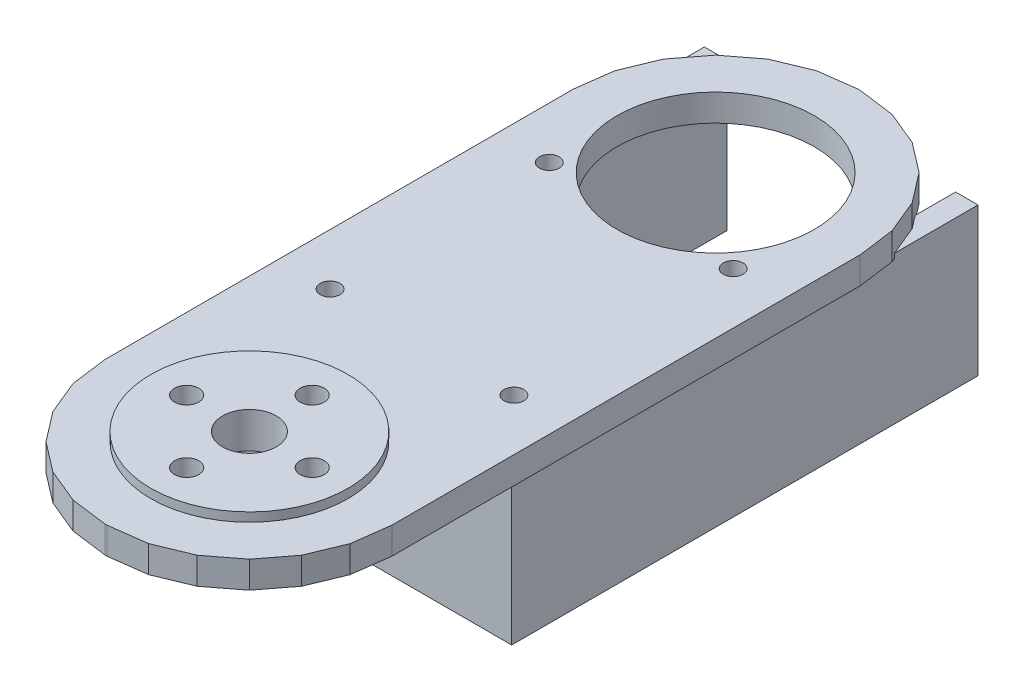
SolidWorks part; units mm, degrees
ref_plane "Front Plane" through (0, 0, 0) normal (0, 0, 1) x (1, 0, 0)
ref_plane "Top Plane" through (0, 0, 0) normal (0, 1, 0) x (1, 0, 0)
ref_plane "Right Plane" through (0, 0, 0) normal (1, 0, 0) x (0, 0, -1)
ref_plane "PY_m1_100" through (0, -1.1, 0) normal (0, 1, 0) x (1, 0, 0)
sketch "S_cyl1" plane through (0, -1.1, 0) normal (0, 1, 0) x (1, 0, 0)
  circle A0 centre (0, 0) radius 11
  dimension "D1_S_cyl1" = 22
extrude "Boss_1" add sketch "S_cyl1" along normal blind 1.1
ref_plane "PY_m4_000" through (0, -4, 0) normal (0, 1, 0) x (1, 0, 0)
sketch "S_prism2" plane through (0, -4, 0) normal (0, 1, 0) x (1, 0, 0)
  line L0 (-16, -0.1) -> (-15.458, -4.215)
  line L1 (-15.458, -4.215) -> (-13.87, -8.05)
  line L2 (-13.87, -8.05) -> (-11.343, -11.343)
  line L3 (-11.343, -11.343) -> (-8.05, -13.87)
  line L4 (-8.05, -13.87) -> (-4.215, -15.458)
  line L5 (-4.215, -15.458) -> (-0.1, -16)
  line L6 (-0.1, -16) -> (0.1, -16)
  line L7 (0.1, -16) -> (4.215, -15.458)
  line L8 (4.215, -15.458) -> (8.05, -13.87)
  line L9 (8.05, -13.87) -> (11.343, -11.343)
  line L10 (11.343, -11.343) -> (13.87, -8.05)
  line L11 (13.87, -8.05) -> (15.458, -4.215)
  line L12 (15.458, -4.215) -> (16, -0.1)
  line L13 (16, -0.1) -> (16, 52.1)
  line L14 (16, 52.1) -> (15.458, 56.215)
  line L15 (15.458, 56.215) -> (13.87, 60.05)
  line L16 (13.87, 60.05) -> (11.343, 63.343)
  line L17 (11.343, 63.343) -> (8.05, 65.87)
  line L18 (8.05, 65.87) -> (4.215, 67.458)
  line L19 (4.215, 67.458) -> (0.1, 68)
  line L20 (0.1, 68) -> (-0.1, 68)
  line L21 (-0.1, 68) -> (-4.215, 67.458)
  line L22 (-4.215, 67.458) -> (-8.05, 65.87)
  line L23 (-8.05, 65.87) -> (-11.343, 63.343)
  line L24 (-11.343, 63.343) -> (-13.87, 60.05)
  line L25 (-13.87, 60.05) -> (-15.458, 56.215)
  line L26 (-15.458, 56.215) -> (-16, 52.1)
  line L27 (-16, 52.1) -> (-16, -0.1)
  dimension "P1" = 16
  dimension "P2" = 0.1
  dimension "P3" = 15.458
  dimension "P4" = 4.215
  dimension "P5" = 13.87
  dimension "P6" = 8.05
  dimension "P7" = 11.343
  dimension "P8" = 11.343
  dimension "P9" = 8.05
  dimension "P10" = 13.87
  dimension "P11" = 4.215
  dimension "P12" = 15.458
  dimension "P13" = 0.1
  dimension "P14" = 16
  dimension "P15" = 0.1
  dimension "P16" = 16
  dimension "P17" = 4.215
  dimension "P18" = 15.458
  dimension "P19" = 8.05
  dimension "P20" = 13.87
  dimension "P21" = 11.343
  dimension "P22" = 11.343
  dimension "P23" = 13.87
  dimension "P24" = 8.05
  dimension "P25" = 15.458
  dimension "P26" = 4.215
  dimension "P27" = 16
  dimension "P28" = 0.1
  dimension "P29" = 16
  dimension "P30" = 52.1
  dimension "P31" = 15.458
  dimension "P32" = 56.215
  dimension "P33" = 13.87
  dimension "P34" = 60.05
  dimension "P35" = 11.343
  dimension "P36" = 63.343
  dimension "P37" = 8.05
  dimension "P38" = 65.87
  dimension "P39" = 4.215
  dimension "P40" = 67.458
  dimension "P41" = 0.1
  dimension "P42" = 68
  dimension "P43" = 0.1
  dimension "P44" = 68
  dimension "P45" = 4.215
  dimension "P46" = 67.458
  dimension "P47" = 8.05
  dimension "P48" = 65.87
  dimension "P49" = 11.343
  dimension "P50" = 63.343
  dimension "P51" = 13.87
  dimension "P52" = 60.05
  dimension "P53" = 15.458
  dimension "P54" = 56.215
  dimension "P55" = 16
  dimension "P56" = 52.1
extrude "Boss_2" add sketch "S_prism2" along normal blind 3
ref_plane "PZ_m66_000" through (0, 0, -66) normal (0, 0, 1) x (1, 0, 0)
sketch "S_box3" plane through (0, 0, -66) normal (0, 0, 1) x (1, 0, 0)
  line L0 (12.76, -20) -> (15.26, -20)
  line L1 (15.26, -20) -> (15.26, -3.5)
  line L2 (15.26, -3.5) -> (12.76, -3.5)
  line L3 (12.76, -3.5) -> (12.76, -20)
  dimension "P1" = 12.76
  dimension "P2" = 20
  dimension "P3" = 15.26
  dimension "P4" = 20
  dimension "P5" = 15.26
  dimension "P6" = 3.5
  dimension "P7" = 12.76
  dimension "P8" = 3.5
extrude "Boss_3" add sketch "S_box3" along normal blind 52.01
sketch "S_box4" plane through (0, 0, -66) normal (0, 0, 1) x (1, 0, 0)
  line L0 (-15.26, -20) -> (-12.76, -20)
  line L1 (-12.76, -20) -> (-12.76, -3.5)
  line L2 (-12.76, -3.5) -> (-15.26, -3.5)
  line L3 (-15.26, -3.5) -> (-15.26, -20)
  dimension "P1" = 15.26
  dimension "P2" = 20
  dimension "P3" = 12.76
  dimension "P4" = 20
  dimension "P5" = 12.76
  dimension "P6" = 3.5
  dimension "P7" = 15.26
  dimension "P8" = 3.5
extrude "Boss_4" add sketch "S_box4" along normal blind 52.01
ref_plane "PZ_m16_490" through (0, 0, -16.49) normal (0, 0, 1) x (1, 0, 0)
sketch "S_box5" plane through (0, 0, -16.49) normal (0, 0, 1) x (1, 0, 0)
  line L0 (-15.26, -20) -> (15.26, -20)
  line L1 (15.26, -20) -> (15.26, -3.5)
  line L2 (15.26, -3.5) -> (-15.26, -3.5)
  line L3 (-15.26, -3.5) -> (-15.26, -20)
  dimension "P1" = 15.26
  dimension "P2" = 20
  dimension "P3" = 15.26
  dimension "P4" = 20
  dimension "P5" = 15.26
  dimension "P6" = 3.5
  dimension "P7" = 15.26
  dimension "P8" = 3.5
extrude "Boss_5" add sketch "S_box5" along normal blind 2.5
ref_plane "PY_m4_100" through (0, -4.1, 0) normal (0, 1, 0) x (1, 0, 0)
sketch "S_hole6" plane through (0, -4.1, 0) normal (0, 1, 0) x (1, 0, 0)
  circle A0 centre (0, 0) radius 3
  dimension "D1_S_hole6" = 6
extrude "Hole_6" cut sketch "S_hole6" along normal blind 4.2
sketch "S_hole7" plane through (0, -4.1, 0) normal (0, 1, 0) x (1, 0, 0)
  circle A0 centre (7, 0) radius 1.35
  dimension "D1_S_hole7" = 2.7
  dimension "P2" = 7
extrude "Hole_7" cut sketch "S_hole7" along normal blind 4.2
sketch "S_hole8" plane through (0, -4.1, 0) normal (0, 1, 0) x (1, 0, 0)
  circle A0 centre (0, -7) radius 1.35
  dimension "D1_S_hole8" = 2.7
  dimension "P2" = 7
extrude "Hole_8" cut sketch "S_hole8" along normal blind 4.2
sketch "S_hole9" plane through (0, -4.1, 0) normal (0, 1, 0) x (1, 0, 0)
  circle A0 centre (-7, 0) radius 1.35
  dimension "D1_S_hole9" = 2.7
  dimension "P2" = 7
extrude "Hole_9" cut sketch "S_hole9" along normal blind 4.2
sketch "S_hole10" plane through (0, -4.1, 0) normal (0, 1, 0) x (1, 0, 0)
  circle A0 centre (0, 7) radius 1.35
  dimension "D1_S_hole10" = 2.7
  dimension "P2" = 7
extrude "Hole_10" cut sketch "S_hole10" along normal blind 4.2
sketch "S_hole11" plane through (0, -4.1, 0) normal (0, 1, 0) x (1, 0, 0)
  circle A0 centre (0, 52) radius 11
  dimension "D1_S_hole11" = 22
  dimension "P2" = 52
extrude "Hole_11" cut sketch "S_hole11" along normal blind 3.2
sketch "S_hole12" plane through (0, -4.1, 0) normal (0, 1, 0) x (1, 0, 0)
  circle A0 centre (-10.25, 43.7) radius 1.1
  dimension "D1_S_hole12" = 2.2
  dimension "P2" = 10.25
  dimension "P3" = 43.7
extrude "Hole_12" cut sketch "S_hole12" along normal blind 3.2
sketch "S_hole13" plane through (0, -4.1, 0) normal (0, 1, 0) x (1, 0, 0)
  circle A0 centre (10.25, 43.7) radius 1.1
  dimension "D1_S_hole13" = 2.2
  dimension "P2" = 10.25
  dimension "P3" = 43.7
extrude "Hole_13" cut sketch "S_hole13" along normal blind 3.2
sketch "S_hole14" plane through (0, -4.1, 0) normal (0, 1, 0) x (1, 0, 0)
  circle A0 centre (-10.25, 19.25) radius 1.1
  dimension "D1_S_hole14" = 2.2
  dimension "P2" = 10.25
  dimension "P3" = 19.25
extrude "Hole_14" cut sketch "S_hole14" along normal blind 3.2
sketch "S_hole15" plane through (0, -4.1, 0) normal (0, 1, 0) x (1, 0, 0)
  circle A0 centre (10.25, 19.25) radius 1.1
  dimension "D1_S_hole15" = 2.2
  dimension "P2" = 10.25
  dimension "P3" = 19.25
extrude "Hole_15" cut sketch "S_hole15" along normal blind 3.2
equation "\"plate_t\" = 3"
equation "\"clearance\" = 0.4"
